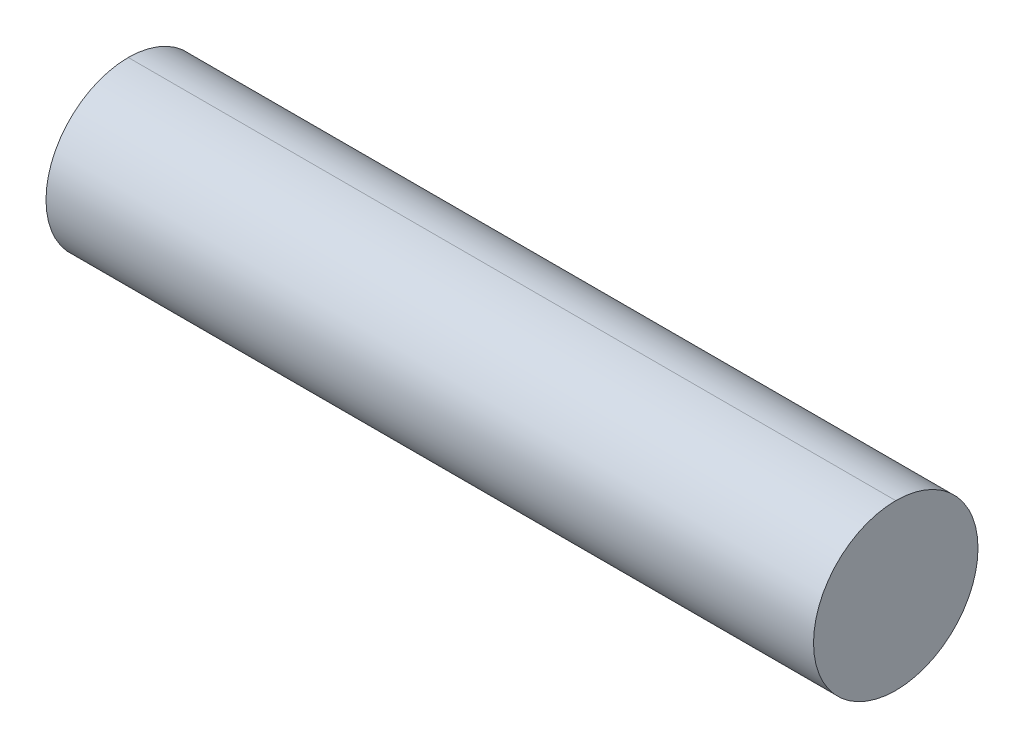
SolidWorks part; units mm, degrees
material "AISI 4340 Steel, normalized"
ref_plane "Front Plane" through (0, 0, 0) normal (0, 0, 1) x (1, 0, 0)
ref_plane "Top Plane" through (0, 0, 0) normal (0, 1, 0) x (1, 0, 0)
ref_plane "Right Plane" through (0, 0, 0) normal (1, 0, 0) x (0, 0, -1)
sketch "Sketch1" plane through (0, 0, 0) normal (1, 0, 0) x (0, 0, -1)
  circle A0 centre (0, 0) radius 19.05
  dimension "D1" = 38.1
extrude "Boss-Extrude1" add sketch "Sketch1" along normal blind 177.8
split line "Split Line1"
